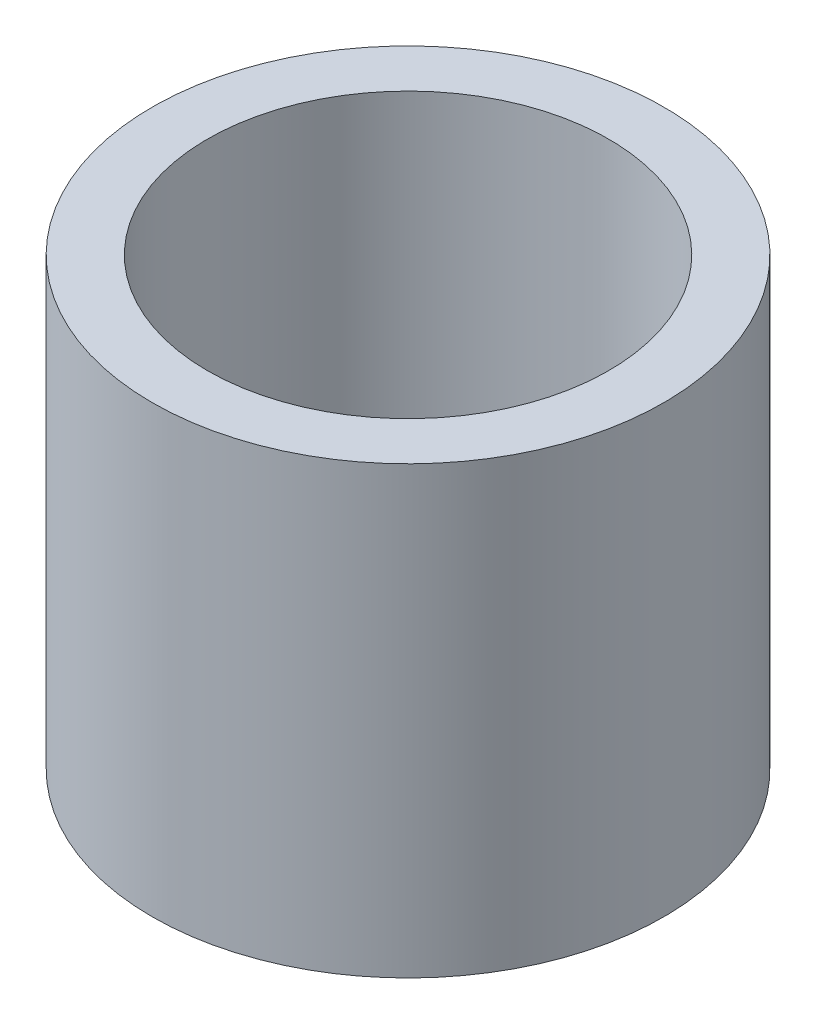
SolidWorks part; units mm, degrees
material "PET"
ref_plane "Front Plane" through (0, 0, 0) normal (0, 0, 1) x (1, 0, 0)
ref_plane "Top Plane" through (0, 0, 0) normal (0, 1, 0) x (1, 0, 0)
ref_plane "Right Plane" through (0, 0, 0) normal (1, 0, 0) x (0, 0, -1)
sketch "Sketch1" plane through (0, 0, 0) normal (0, 1, 0) x (1, 0, 0)
  circle A0 centre (0, 0) radius 3.175
  circle A1 centre (0, 0) radius 2.4892
  dimension "D1" = 6.35
  dimension "D2" = 4.9784
extrude "Boss-Extrude1" add sketch "Sketch1" along normal blind 5.525
